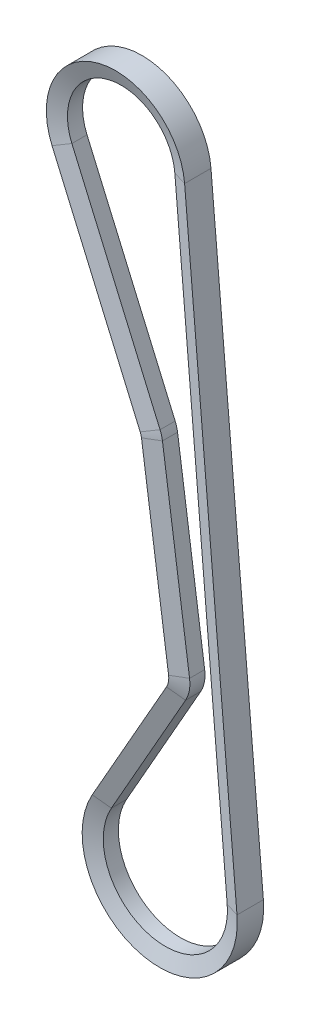
SolidWorks part; units mm, degrees
ref_plane "Front Plane" through (0, 0, 0) normal (0, 0, 1) x (1, 0, 0)
ref_plane "Top Plane" through (0, 0, 0) normal (0, 1, 0) x (1, 0, 0)
ref_plane "Right Plane" through (0, 0, 0) normal (1, 0, 0) x (0, 0, -1)
sketch "Sketch2" plane through (0, 0, 0) normal (0, 0, 1) x (1, 0, 0)
  line L0 (0, 0) -> (1, 0) construction
  line L1 (0, 0) -> (0, 1) construction
  line L12 (24.9075, 2.1491) -> (43.818, -217.0161)
  line L14 (-8.422, -205.5888) -> (18.3642, -158.4542)
  line L15 (19.1311, -154.4289) -> (9.3433, -85.1166)
  line L16 (8.8835, -83.4827) -> (-22.9441, -9.9281)
  arc A4 (43.818, -217.0161) -> (-8.422, -205.5888) centre (15.9216, -219.4231) cw
  arc A7 (-22.9441, -9.9281) -> (24.9075, 2.1491) centre (0, 0) cw
  arc A8 (18.3642, -158.4542) -> (19.1311, -154.4289) centre (12.8435, -155.3168) ccw
  arc A9 (9.3433, -85.1166) -> (8.8835, -83.4827) centre (3.0557, -86.0045) ccw
ref_plane "Plane4" through (-22.9441, -9.9281, 0) normal (-0.3971, 0.9178, 0) x (0.9178, 0.3971, 0)
sketch "Sketch3" plane through (-22.9441, -9.9281, 0) normal (-0.3971, 0.9178, 0) x (0.9178, 0.3971, 0)
  line L0 (0, -4.7625) -> (0, 4.7625)
  line L1 (0, -4.7625) -> (5.588, -2.7286)
  line L2 (5.588, -2.7286) -> (5.588, 2.7286)
  line L3 (5.588, 2.7286) -> (0, 4.7625)
  line L4 (0, 0) -> (5.588, 0) construction
  dimension "D1" = 9.525
  dimension "D2" = 5.588
  dimension "D3" = 40
sweep "Sweep1" add profiles "Sketch3" path "Sketch2"
